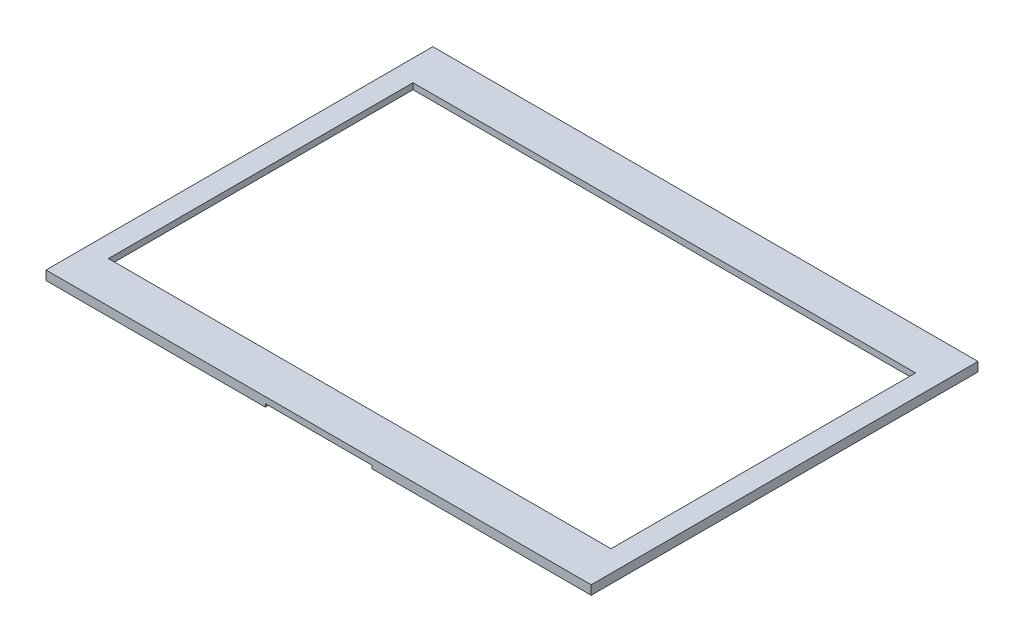
SolidWorks part; units mm, degrees
ref_plane "Front Plane" through (0, 0, 0) normal (0, 0, 1) x (1, 0, 0)
ref_plane "Top Plane" through (0, 0, 0) normal (0, 1, 0) x (1, 0, 0)
ref_plane "Right Plane" through (0, 0, 0) normal (1, 0, 0) x (0, 0, -1)
sketch "Sketch1" plane through (0, 0, 0) normal (0, 1, 0) x (1, 0, 0)
  line L1 (0, 0) -> (179, 0)
  line L2 (0, 0) -> (0, 127)
  line L3 (0, 127) -> (179, 127)
  line L4 (179, 0) -> (179, 127)
  line L5 (3.5, 115.5) -> (175.5, 115.5)
  line L6 (3.5, 115.5) -> (3.5, 3.5)
  line L7 (3.5, 3.5) -> (175.5, 3.5)
  line L8 (175.5, 115.5) -> (175.5, 3.5)
  line L9 (172, 13.5) -> (7, 13.5)
  line L10 (172, 13.5) -> (172, 113.5)
  line L11 (172, 113.5) -> (7, 113.5)
  line L12 (7, 13.5) -> (7, 113.5)
  line L13 (72, 3.5) -> (107, 3.5)
  line L14 (72, 3.5) -> (72, 0)
  line L15 (72, 0) -> (107, 0)
  line L16 (107, 3.5) -> (107, 0)
  point P13 (89.5, 13.5)
  point P14 (89.5, 3.5)
  point P15 (89.5, 0)
  point P16 (7, 63.5)
  point P17 (0, 63.5)
  point P22 (89.5, 0)
  dimension "D1" = 127
  dimension "D2" = 179
  dimension "D3" = 172
  dimension "D4" = 112
  dimension "D5" = 100
  dimension "D6" = 165
  dimension "D7" = 10
  dimension "D8" = 35
extrude "Boss-Extrude1" add sketch "Sketch1" along normal blind 3 contours L2 L3 L4 L1 | L12 L11 L10 L9
extrude "Cut-Extrude1" cut sketch "Sketch1<3>" along normal blind 1 contours L7 L8 L5 L6 | L16 L15 L14 L13
sketch "Sketch1<3>" plane through (0, 0, 0) normal (0, 1, 0) x (1, 0, 0) same geometry as "Sketch1"
